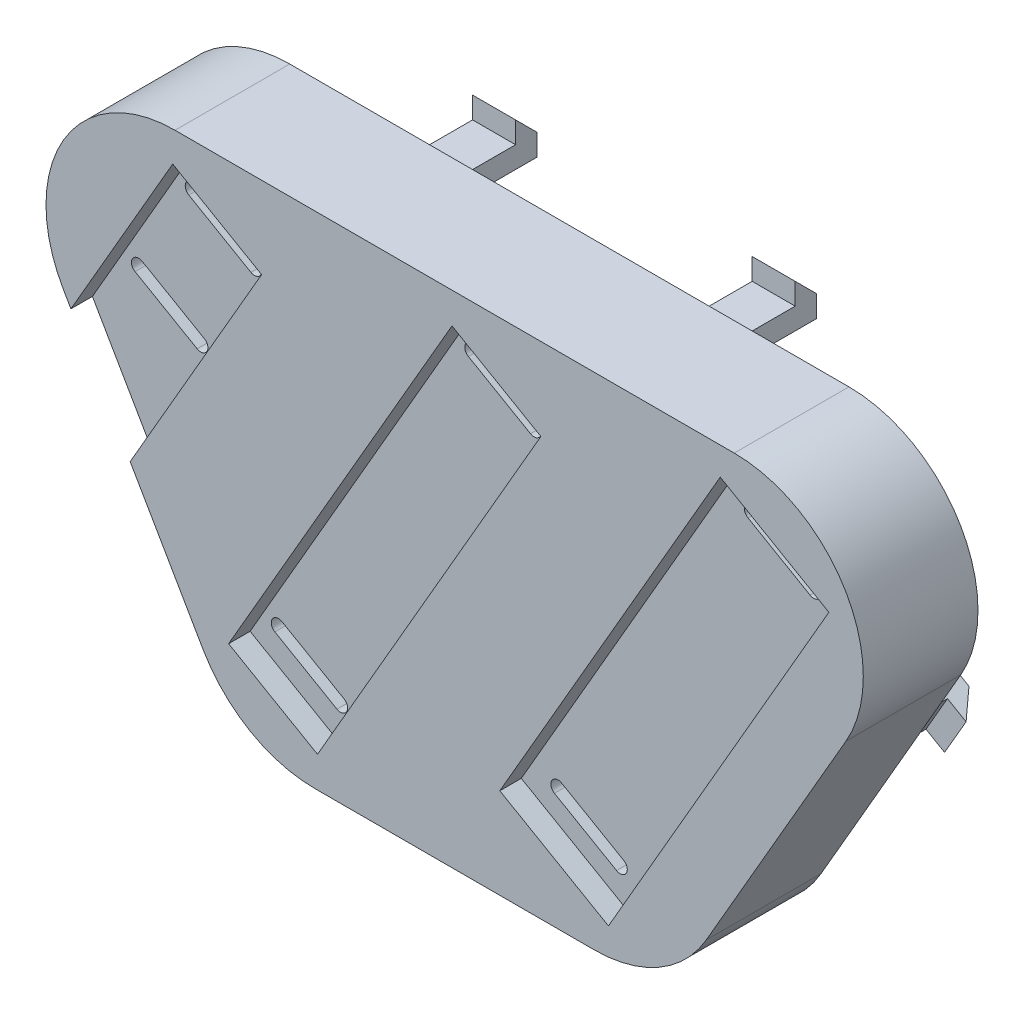
SolidWorks part; units mm, degrees
ref_plane "Front Plane" through (0, 0, 0) normal (0, 0, 1) x (1, 0, 0)
ref_plane "Top Plane" through (0, 0, 0) normal (0, 1, 0) x (1, 0, 0)
ref_plane "Right Plane" through (0, 0, 0) normal (1, 0, 0) x (0, 0, -1)
sketch "Sketch1" plane through (0, 0, 0) normal (0, 0, 1) x (1, 0, 0)
  line L0 (0, 0) -> (-19.5, 0) construction
  line L1 (-9.75, -16.8875) -> (-29.25, -16.8875) construction
  line L2 (0, 0) -> (-9.75, -16.8875) construction
  line L3 (-9.75, -16.8875) -> (-19.5, 0) construction
  line L4 (-19.5, 0) -> (-29.25, -16.8875) construction
  line L5 (-29.25, -16.8875) -> (-39, 0) construction
  line L6 (-39, 0) -> (-19.5, 0) construction
  line L7 (8.9827, 0.5584) -> (-5.4199, -24.3875) construction
  line L8 (-5.4199, -24.3875) -> (-33.5801, -24.3875) construction
  line L9 (-33.5801, -24.3875) -> (-47.9827, 0.5584) construction
  line L10 (-43.9749, 7.5) -> (4.9749, 7.5) construction
  line L11 (7.7942, -4.5) -> (-1.9558, -21.3875)
  line L12 (-9.75, -25.8875) -> (-29.25, -25.8875)
  line L13 (-37.0442, -21.3875) -> (-46.7942, -4.5)
  line L14 (-39, 9) -> (0, 9)
  line L15 (1.7814, -11.9145) -> (3.0804, -12.6645) construction
  line L16 (-19.5, -24.3875) -> (-19.5, -25.8875) construction
  line L17 (-40.7814, -11.9145) -> (-42.0804, -12.6645) construction
  line L18 (-19.5, 7.5) -> (-19.5, 9) construction
  circle A0 centre (-29.25, -16.8875) radius 7.5
  circle A1 centre (-19.5, 0) radius 7.5
  circle A2 centre (0, 0) radius 7.5
  circle A3 centre (0, 0) radius 7.5
  circle A4 centre (-9.75, -16.8875) radius 7.5
  circle A5 centre (-39, 0) radius 7.5
  arc A6 (7.7942, -4.5) -> (0, 9) centre (0, 0) ccw
  arc A7 (-39, 9) -> (-46.7942, -4.5) centre (-39, 0) ccw
  arc A8 (-1.9558, -21.3875) -> (-9.75, -25.8875) centre (-9.75, -16.8875) cw
  arc A9 (-29.25, -25.8875) -> (-37.0442, -21.3875) centre (-29.25, -16.8875) cw
  point P28 (1.7814, -11.9145)
  point P30 (-19.5, -24.3875)
  point P32 (-40.7814, -11.9145)
  point P35 (-19.5, 9)
  dimension "D2" = 15
  dimension "D3" = 19.5
  dimension "D4" = 1.5
  dimension "D5" = 1.5
  dimension "D1" = 0.25
extrude "Boss-Extrude1" add sketch "Sketch1" along normal blind 5
sketch "Sketch2" plane through (0, 0, 5) normal (0, 0, 1) x (1, 0, 0)
  line L0 (-1.9558, -21.3875) -> (7.7942, -4.5) construction
  line L1 (0, 9) -> (-39, 9) construction
  line L2 (-46.7942, -4.5) -> (-37.0442, -21.3875) construction
  line L3 (-29.25, -25.8875) -> (-9.75, -25.8875) construction
  line L4 (-1.9558, -21.3875) -> (7.7942, -4.5)
  line L5 (0, 9) -> (-39, 9)
  line L6 (-46.7942, -4.5) -> (-37.0442, -21.3875)
  line L7 (-29.25, -25.8875) -> (-9.75, -25.8875)
  line L8 (4.0401, 1.9976) -> (-0.2901, 4.4976) construction
  line L9 (3.7901, 1.5646) -> (-0.5401, 4.0646)
  line L10 (4.2901, 2.4306) -> (-0.0401, 4.9306)
  line L11 (-9.4599, -21.3851) -> (-13.7901, -18.8851) construction
  line L12 (-9.7099, -21.8181) -> (-14.0401, -19.3181)
  line L13 (-9.2099, -20.9521) -> (-13.5401, -18.4521)
  line L14 (1.875, 3.2476) -> (-11.625, -20.1351) construction
  line L15 (-31.125, -20.1351) -> (-29.25, -16.8875) construction
  line L16 (0, 0) -> (1.875, 3.2476) construction
  line L17 (1.875, 3.2476) -> (3.75, 6.4952) construction
  line L18 (-11.625, -20.1351) -> (-13.5, -23.3827) construction
  line L19 (-11.625, -20.1351) -> (-9.75, -16.8875) construction
  line L20 (-17.625, 3.2476) -> (-15.75, 6.4952) construction
  line L21 (-17.625, 3.2476) -> (-31.125, -20.1351) construction
  line L22 (-19.5, 0) -> (-17.625, 3.2476) construction
  line L23 (-31.125, -20.1351) -> (-33, -23.3827) construction
  line L24 (-15.4599, 1.9976) -> (-19.7901, 4.4976) construction
  line L25 (-15.7099, 1.5646) -> (-20.0401, 4.0646)
  line L26 (-15.2099, 2.4306) -> (-19.5401, 4.9306)
  line L27 (-28.9599, -21.3851) -> (-33.2901, -18.8851) construction
  line L28 (-29.2099, -21.8181) -> (-33.5401, -19.3181)
  line L29 (-28.7099, -20.9521) -> (-33.0401, -18.4521)
  line L30 (-34.9599, 1.9976) -> (-39.2901, 4.4976) construction
  line L31 (-35.2099, 1.5646) -> (-39.5401, 4.0646)
  line L32 (-34.7099, 2.4306) -> (-39.0401, 4.9306)
  line L33 (-38.7099, -4.4976) -> (-43.0401, -1.9976) construction
  line L34 (-38.9599, -4.9306) -> (-43.2901, -2.4306)
  line L35 (-38.4599, -4.0646) -> (-42.7901, -1.5646)
  line L36 (-37.125, 3.2476) -> (-40.875, -3.2476) construction
  line L37 (-37.125, 3.2476) -> (-35.25, 6.4952) construction
  line L38 (-40.875, -3.2476) -> (-42.75, -6.4952) construction
  line L39 (-37.125, 3.2476) -> (-39, 0) construction
  arc A0 (-9.75, -25.8875) -> (-1.9558, -21.3875) centre (-9.75, -16.8875) ccw construction
  arc A1 (7.7942, -4.5) -> (0, 9) centre (0, 0) ccw construction
  arc A2 (-39, 9) -> (-46.7942, -4.5) centre (-39, 0) ccw construction
  arc A3 (-37.0442, -21.3875) -> (-29.25, -25.8875) centre (-29.25, -16.8875) ccw construction
  arc A4 (-9.75, -25.8875) -> (-1.9558, -21.3875) centre (-9.75, -16.8875) ccw
  arc A5 (7.7942, -4.5) -> (0, 9) centre (0, 0) ccw
  arc A6 (-39, 9) -> (-46.7942, -4.5) centre (-39, 0) ccw
  arc A7 (-37.0442, -21.3875) -> (-29.25, -25.8875) centre (-29.25, -16.8875) ccw
  circle A8 centre (-39, 0) radius 7.5 construction
  circle A9 centre (-29.25, -16.8875) radius 7.5 construction
  circle A10 centre (-19.5, 0) radius 7.5 construction
  circle A11 centre (-9.75, -16.8875) radius 7.5 construction
  circle A12 centre (0, 0) radius 7.5 construction
  circle A13 centre (-39, 0) radius 7.5
  circle A14 centre (-29.25, -16.8875) radius 7.5
  circle A15 centre (-19.5, 0) radius 7.5
  circle A16 centre (-9.75, -16.8875) radius 7.5
  circle A17 centre (0, 0) radius 7.5
  arc A18 (3.7901, 1.5646) -> (4.2901, 2.4306) centre (4.0401, 1.9976) ccw
  arc A19 (-0.0401, 4.9306) -> (-0.5401, 4.0646) centre (-0.2901, 4.4976) ccw
  arc A20 (-9.7099, -21.8181) -> (-9.2099, -20.9521) centre (-9.4599, -21.3851) ccw
  arc A21 (-13.5401, -18.4521) -> (-14.0401, -19.3181) centre (-13.7901, -18.8851) ccw
  arc A22 (-15.7099, 1.5646) -> (-15.2099, 2.4306) centre (-15.4599, 1.9976) ccw
  arc A23 (-19.5401, 4.9306) -> (-20.0401, 4.0646) centre (-19.7901, 4.4976) ccw
  arc A24 (-29.2099, -21.8181) -> (-28.7099, -20.9521) centre (-28.9599, -21.3851) ccw
  arc A25 (-33.0401, -18.4521) -> (-33.5401, -19.3181) centre (-33.2901, -18.8851) ccw
  arc A26 (-35.2099, 1.5646) -> (-34.7099, 2.4306) centre (-34.9599, 1.9976) ccw
  arc A27 (-39.0401, 4.9306) -> (-39.5401, 4.0646) centre (-39.2901, 4.4976) ccw
  arc A28 (-38.9599, -4.9306) -> (-38.4599, -4.0646) centre (-38.7099, -4.4976) ccw
  arc A29 (-42.7901, -1.5646) -> (-43.2901, -2.4306) centre (-43.0401, -1.9976) ccw
  point P8 (-37.125, 3.2476)
  point P25 (1.875, 3.2476)
  point P32 (-11.625, -20.1351)
  point P45 (-17.625, 3.2476)
  point P52 (-31.125, -20.1351)
  point P64 (-40.875, -3.2476)
  point P75 (0, 0)
  point P77 (0, 0)
  point P78 (0, 0)
  point P79 (0, 0)
  circle M1 centre (-9.75, -16.8875) radius 7.5
  circle M2 centre (0, 0) radius 7.5
  arc M3 (7.7942, -4.5) -> (0, 9) centre (0, 0) ccw
  line M4 (0, 9) -> (-39, 9)
  arc M5 (-39, 9) -> (-46.7942, -4.5) centre (-39, 0) ccw
  line M6 (-46.7942, -4.5) -> (-37.0442, -21.3875)
  arc M7 (-37.0442, -21.3875) -> (-29.25, -25.8875) centre (-29.25, -16.8875) ccw
  line M8 (-29.25, -25.8875) -> (-9.75, -25.8875)
  arc M9 (-9.75, -25.8875) -> (-1.9558, -21.3875) centre (-9.75, -16.8875) ccw
  line M10 (-1.9558, -21.3875) -> (7.7942, -4.5)
  circle M11 centre (-19.5, 0) radius 7.5
  circle M12 centre (-29.25, -16.8875) radius 7.5
  circle M13 centre (-39, 0) radius 7.5
  dimension "D1" = 1
  dimension "D2" = 5
extrude "Boss-Extrude2" add sketch "Sketch2" along normal blind 1.5 contours A21 L13 A20 L12 M1 | M10 M3 M4 M5 M6 M7 M8 M9 M2 M11 M13 M12 M1 | A19 L10 A18 L9 M2 | A23 L26 A22 L25 M11 | A25 L29 A24 L28 M12 | A29 L35 A28 L34 A27 L32 A26 L31 M13 region at (-5.5841, -24.103, 5) region at (-39, 0, 5) region at (-29.1865, -16.7776, 5) region at (-19.5635, -0.1099, 5) region at (-9.6865, -16.7776, 5) region at (-0.0635, -0.1099, 5)
sketch "Sketch3" plane through (0, 0, 6.5) normal (0, 0, 1) x (1, 0, 0)
  line L0 (-46.7942, -4.5) -> (-37.0442, -21.3875) construction
  line L1 (-29.25, -25.8875) -> (-9.75, -25.8875) construction
  line L2 (-1.9558, -21.3875) -> (7.7942, -4.5) construction
  line L3 (0, 9) -> (-39, 9) construction
  line L4 (-46.7942, -4.5) -> (-37.0442, -21.3875)
  line L5 (-29.25, -25.8875) -> (-9.75, -25.8875)
  line L6 (-1.9558, -21.3875) -> (7.7942, -4.5)
  line L7 (0, 9) -> (-39, 9)
  line L8 (6.6014, 2.6839) -> (-8.7736, -23.9464)
  line L9 (6.6014, 2.6839) -> (-0.9764, 7.0589)
  line L10 (-8.7736, -23.9464) -> (-16.3514, -19.5714)
  line L11 (-0.9764, 7.0589) -> (-16.3514, -19.5714)
  line L12 (6.6014, 2.6839) -> (-16.3514, -19.5714) construction
  line L13 (-8.7736, -23.9464) -> (-0.9764, 7.0589) construction
  line L14 (-11.625, -20.1351) -> (-13.5, -23.3827) construction
  line L15 (-11.625, -20.1351) -> (-13.5, -23.3827) construction
  line L16 (-11.875, -20.5681) -> (-12.5625, -21.7589) construction
  line L17 (-9.7099, -21.8181) -> (-14.0401, -19.3181) construction
  line L18 (-14.2231, -18.6351) -> (-15.4139, -17.9476) construction
  line L19 (1.875, 3.2476) -> (-11.625, -20.1351) construction
  line L20 (1.875, 3.2476) -> (-11.625, -20.1351) construction
  line L21 (-31.125, -20.1351) -> (-33, -23.3827) construction
  line L22 (-17.625, 3.2476) -> (-31.125, -20.1351) construction
  line L23 (-31.125, -20.1351) -> (-33, -23.3827) construction
  line L24 (-17.625, 3.2476) -> (-31.125, -20.1351) construction
  line L25 (-13.4854, 3.2587) -> (-29.0648, -23.7257)
  line L26 (-13.4854, 3.2587) -> (-19.6852, 6.8382)
  line L27 (-29.0648, -23.7257) -> (-35.2646, -20.1462)
  line L28 (-19.6852, 6.8382) -> (-35.2646, -20.1462)
  line L29 (-13.4854, 3.2587) -> (-35.2646, -20.1462) construction
  line L30 (-29.0648, -23.7257) -> (-19.6852, 6.8382) construction
  line L31 (-32.8571, -19.1351) -> (-34.2249, -18.3454) construction
  line L32 (-31.375, -20.5681) -> (-32.1647, -21.9359) construction
  line L33 (-29.2099, -21.8181) -> (-33.5401, -19.3181) construction
  line L34 (-32.9626, 3.2982) -> (-42.1296, -12.5794)
  line L35 (-32.9626, 3.2982) -> (-39.1624, 6.8776)
  line L37 (-39.1624, 6.8776) -> (-46.2627, -5.4206)
  line L38 (-32.9626, 3.2982) -> (-45.5024, -6.7376) construction
  line L39 (-42.1296, -12.5794) -> (-39.1624, 6.8776) construction
  line L40 (-37.125, 3.2476) -> (-40.875, -3.2476) construction
  line L41 (-36.875, 3.6806) -> (-36.0625, 5.0879) construction
  line L42 (-34.7099, 2.4306) -> (-39.0401, 4.9306) construction
  line L43 (-36.0625, 5.0879) -> (-35.25, 6.4952) construction
  arc A0 (-37.0442, -21.3875) -> (-29.25, -25.8875) centre (-29.25, -16.8875) ccw construction
  arc A1 (-9.75, -25.8875) -> (-1.9558, -21.3875) centre (-9.75, -16.8875) ccw construction
  arc A2 (7.7942, -4.5) -> (0, 9) centre (0, 0) ccw construction
  arc A3 (-39, 9) -> (-46.7942, -4.5) centre (-39, 0) ccw construction
  arc A4 (-37.0442, -21.3875) -> (-29.25, -25.8875) centre (-29.25, -16.8875) ccw
  arc A5 (-9.75, -25.8875) -> (-1.9558, -21.3875) centre (-9.75, -16.8875) ccw
  arc A6 (7.7942, -4.5) -> (0, 9) centre (0, 0) ccw
  arc A7 (-39, 9) -> (-46.7942, -4.5) centre (-39, 0) ccw
  arc A8 (-13.5401, -18.4521) -> (-14.0401, -19.3181) centre (-13.7901, -18.8851) ccw construction
  arc A9 (-33.0401, -18.4521) -> (-33.5401, -19.3181) centre (-33.2901, -18.8851) ccw construction
  point P13 (-4.875, -8.4437)
  point P30 (-12.5625, -21.7589)
  point P33 (-4.875, -8.4437)
  point P35 (-24.375, -8.4437)
  point P49 (-24.375, -8.4437)
  point P50 (-40.646, -2.8509)
  line M15 (-1.9558, -21.3875) -> (7.7942, -4.5)
  arc M16 (7.7942, -4.5) -> (0, 9) centre (0, 0) ccw
  line M17 (0, 9) -> (-39, 9)
  arc M18 (-39, 9) -> (-46.7942, -4.5) centre (-39, 0) ccw
  line M19 (-46.7942, -4.5) -> (-37.0442, -21.3875)
  arc M20 (-37.0442, -21.3875) -> (-29.25, -25.8875) centre (-29.25, -16.8875) ccw
  line M21 (-29.25, -25.8875) -> (-9.75, -25.8875)
  arc M22 (-9.75, -25.8875) -> (-1.9558, -21.3875) centre (-9.75, -16.8875) ccw
extrude "Boss-Extrude3" add sketch "Sketch3" along normal blind 1.5 contours L37 L35 L34 L4 L28 L26 L25 L27 L11 L9 L8 L10 M20 M21 M22 M15 M16 M17 M18 M19 region at (-46.2155, 4.1659, 6.5)
sketch "Sketch4" plane through (0, 0, 0) normal (0, 0, -1) x (-1, 0, 0)
  line L0 (29.25, -25.8875) -> (9.75, -25.8875) construction
  line L1 (21, -25.8875) -> (18, -25.8875)
  line L2 (21, -25.8875) -> (21, -22.8875)
  line L3 (21, -22.8875) -> (18, -22.8875)
  line L4 (18, -25.8875) -> (18, -22.8875)
  line L5 (21, -25.8875) -> (18, -22.8875) construction
  line L6 (21, -22.8875) -> (18, -25.8875) construction
  line L7 (29.25, -25.8875) -> (9.75, -25.8875)
  line L8 (0, 9) -> (39, 9) construction
  line L9 (46.7942, -4.5) -> (37.0442, -21.3875) construction
  line L10 (1.9558, -21.3875) -> (-7.7942, -4.5) construction
  line L11 (0, 9) -> (39, 9)
  line L12 (46.7942, -4.5) -> (37.0442, -21.3875)
  line L13 (1.9558, -21.3875) -> (-7.7942, -4.5)
  line L14 (40.0712, -10.1447) -> (42.6692, -11.6447)
  line L15 (40.0712, -10.1447) -> (38.5712, -12.7428)
  line L16 (42.6692, -11.6447) -> (41.1692, -14.2428)
  line L17 (38.5712, -12.7428) -> (41.1692, -14.2428)
  line L18 (40.0712, -10.1447) -> (41.1692, -14.2428) construction
  line L19 (42.6692, -11.6447) -> (38.5712, -12.7428) construction
  line L20 (-1.0712, -10.1447) -> (-3.6692, -11.6447)
  line L21 (-1.0712, -10.1447) -> (0.4288, -12.7428)
  line L22 (-3.6692, -11.6447) -> (-2.1692, -14.2428)
  line L23 (0.4288, -12.7428) -> (-2.1692, -14.2428)
  line L24 (-1.0712, -10.1447) -> (-2.1692, -14.2428) construction
  line L25 (-3.6692, -11.6447) -> (0.4288, -12.7428) construction
  line L26 (41.9192, -12.9437) -> (3.9115, 9) construction
  line L27 (11.25, 6) -> (8.25, 6)
  line L28 (11.25, 6) -> (11.25, 9)
  line L29 (11.25, 9) -> (8.25, 9)
  line L30 (8.25, 6) -> (8.25, 9)
  line L31 (11.25, 6) -> (8.25, 9) construction
  line L32 (11.25, 9) -> (8.25, 6) construction
  line L33 (30.75, 6) -> (27.75, 6)
  line L34 (30.75, 6) -> (30.75, 9)
  line L35 (30.75, 9) -> (27.75, 9)
  line L36 (27.75, 6) -> (27.75, 9)
  line L37 (30.75, 6) -> (27.75, 9) construction
  line L38 (30.75, 9) -> (27.75, 6) construction
  line L39 (-2.9192, -12.9437) -> (35.0885, 9) construction
  point P0 (19.5, -24.3875)
  point P5 (9.75, 7.5)
  point P8 (19.5, -25.8875)
  point P15 (40.6202, -12.1937)
  point P16 (-1.6202, -12.1937)
  point P29 (29.25, 7.5)
  point P36 (0, 0)
  point P37 (0, 0)
  point P38 (0, 0)
  point P42 (24.75, 7.5)
  point P43 (24.75, 7.5)
  point P44 (24.75, 7.5)
  point P46 (0, 0)
  point P48 (0, 0)
  line M35 (9.75, -25.8875) -> (29.25, -25.8875)
  dimension "D1" = 3
  dimension "D2" = 3
extrude "Boss-Extrude4" add sketch "Sketch4" along normal blind 6 contours L15 L17 L12 L14 | L4 L2 L3 M35 | L23 L21 L20 L13 | L30 L27 L28 L11 | L36 L33 L34 L11 region at (-19.5, -24.3875, 0) region at (-29.25, 7.5, 0) region at (-9.75, 7.5, 0) region at (-40.6202, -12.1937, 0) region at (1.6202, -12.1937, 0)
sketch "Sketch5" plane through (-5.625, 9.7428, 0) normal (-0.5, 0.866, 0) x (0.866, 0.5, 0)
  line L0 (-42.775, 6) -> (-39.775, 6) construction
  line L1 (-42.775, 0) -> (-41.275, 0)
  line L2 (-42.775, 0) -> (-42.775, 4.5)
  line L3 (-42.775, 4.5) -> (-41.275, 4.5)
  line L4 (-41.275, 0) -> (-41.275, 4.5)
  line L5 (-42.775, 4.5) -> (-41.275, 6)
  point P9 (-41.275, 6)
  line M2 (-42.775, 0) -> (-39.775, 0)
  line M4 (-39.775, 6) -> (-42.775, 6)
  line M5 (-42.775, 6) -> (-42.775, 0)
  dimension "D1" = 4.5
extrude "Cut-Extrude1" cut sketch "Sketch5" against normal up to next contours L4 L3 M2 M5 | L5 M5 M4 region at (-42.0197, -11.2697, -2.25) region at (-42.2362, -11.3947, -5.5)
sketch "Sketch7" plane through (-30.75, 0, 0) normal (-1, 0, 0) x (0, 0, 1)
  line L0 (-6, 6) -> (-6, 9) construction
  line L1 (0, 9) -> (-4.5, 9)
  line L2 (0, 9) -> (0, 7.5)
  line L3 (0, 7.5) -> (-4.5, 7.5)
  line L4 (-4.5, 9) -> (-4.5, 7.5)
  line L5 (-4.5, 9) -> (-6, 7.5)
  point P9 (-6, 7.5)
  line M3 (0, 6) -> (0, 9)
  line M4 (0, 9) -> (-6, 9)
  line M5 (-6, 9) -> (-6, 6)
  dimension "D1" = 4.5
extrude "Cut-Extrude2" cut sketch "Sketch7" against normal up to next contours L4 L3 M4 M3 | L5 M4 M5 region at (-30.75, 8.25, -2.25) region at (-30.75, 8.5, -5.5)
ref_axis "Axis1" through (-19.5, -25.8875, -6) along (0, 0, 1)
ref_plane "Plane1" through (-19.5, 0, 0) normal (-1, 0, 0) x (0, 0, 1)
mirror "Mirror1" about plane through (-19.5, 0, 0) normal (-1, 0, 0) of "Cut-Extrude2", "Cut-Extrude1"
sketch "Sketch8" plane through (-21, 0, 0) normal (-1, 0, 0) x (0, 0, 1)
  line L0 (-4.5, -25.8875) -> (-6, -24.3875)
  line L1 (0, -25.8875) -> (-4.5, -25.8875)
  line L2 (0, -25.8875) -> (0, -24.3875)
  line L3 (0, -24.3875) -> (-4.5, -24.3875)
  line L4 (-4.5, -25.8875) -> (-4.5, -24.3875)
  line L5 (0, -25.8875) -> (0, -22.8875) construction
  line L6 (-6, -25.8875) -> (-6, -22.8875) construction
  line M2 (0, -25.8875) -> (0, -22.8875)
  line M4 (-6, -22.8875) -> (-6, -25.8875)
  line M5 (-6, -25.8875) -> (0, -25.8875)
  dimension "D1" = 4.5
extrude "Cut-Extrude3" cut sketch "Sketch8" against normal up to next contours L0 M5 M4 | L4 L3 M5 M2 region at (-21, -25.3875, -5.5) region at (-21, -25.1375, -2.25)
equation "\"D3@Sketch1\"=\"D2@Sketch1\"+4.5"
equation "\"D1@Sketch2\"=.65+.35"
